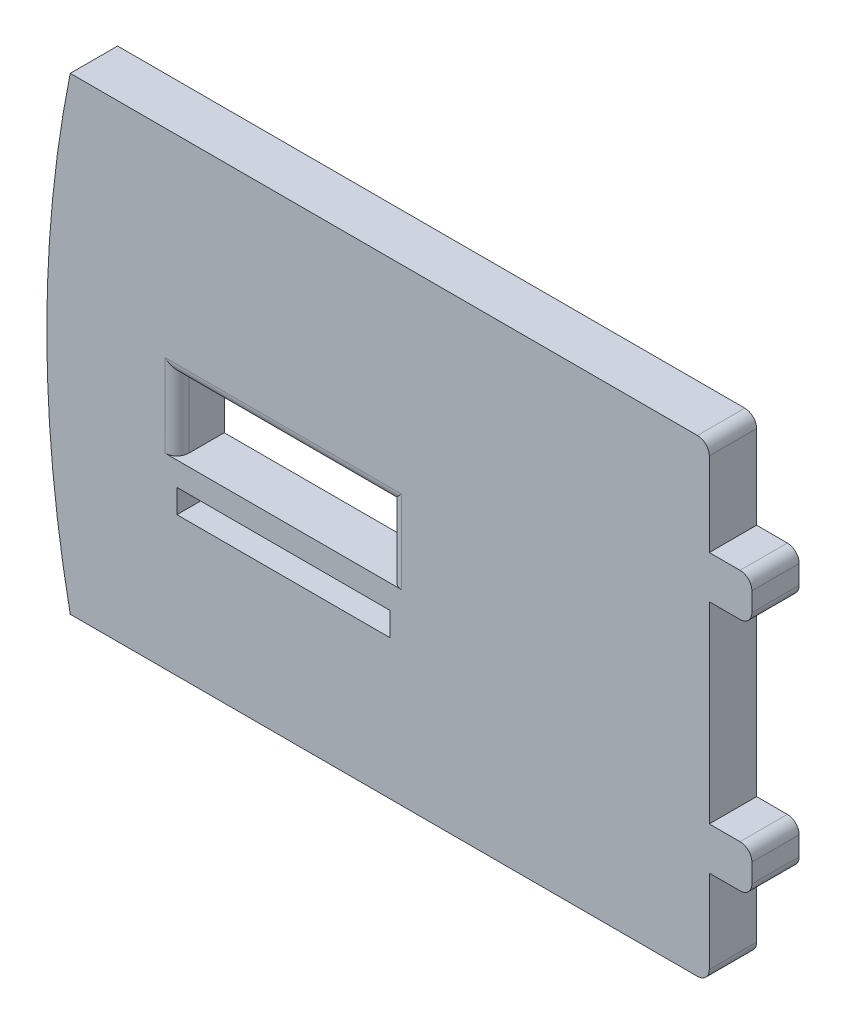
SolidWorks part; units mm, degrees
note: The reader was unsure of these and kept them because the rebuilt part matched: shared geometry of "Sketch1<3>", "Sketch1<4>", "Sketch1<9>".
ref_plane "Front Plane" through (0, 0, 0) normal (0, 0, 1) x (1, 0, 0)
ref_plane "Top Plane" through (0, 0, 0) normal (0, 1, 0) x (1, 0, 0)
ref_plane "Right Plane" through (0, 0, 0) normal (1, 0, 0) x (0, 0, -1)
sketch "Sketch1" plane through (0, 0, 0) normal (0, 0, 1) x (1, 0, 0)
  line L0 (0, 0) -> (-40, 0)
  line L1 (0, 0) -> (20, 0)
  line L2 (-10, 0) -> (-10, 9.9)
  line L3 (-44.5, 2) -> (-35.5, 2)
  line L4 (-44.5, 2) -> (-44.5, -2)
  line L5 (-44.5, -2) -> (-35.5, -2)
  line L6 (-35.5, 2) -> (-35.5, -2)
  line L7 (-44.5, 2) -> (-35.5, -2) construction
  line L8 (-44.5, -2) -> (-35.5, 2) construction
  line L10 (-10, 0) -> (-10, -9.9)
  line L13 (-22, 9.9) -> (-22, -9.9)
  line L14 (-10, 0) -> (-10, 9.9)
  line L15 (-10, 0) -> (-10, -9.9)
  line L16 (-10, -9.9) -> (-49.0101, -9.9)
  line L17 (-10, 9.9) -> (-49.0101, 9.9)
  circle A0 centre (0, 0) radius 50
  circle A1 centre (0, 0) radius 10
  dimension "D1" = 100
  dimension "D5" = 20
  dimension "D2" = 4
  dimension "D3" = 9
  dimension "D4" = 40
extrude "Boss-Extrude1" add sketch "Sketch1" against normal blind 2 contours A0
extrude "Boss-Extrude2" add sketch "Sketch1<3>" along normal blind 5
sketch "Sketch1<3>" plane through (0, 0, 0) normal (0, 0, 1) x (1, 0, 0) same geometry as "Sketch1"
ref_plane "Plane1" through (-35.5, 0, 0) normal (1, 0, 0) x (0, 0, -1)
sketch "Sketch2" plane through (-35.5, 0, 0) normal (1, 0, 0) x (0, 0, -1)
  line L0 (-5, 2) -> (0, -2)
  line L1 (0, 0) -> (-2.5, 0)
  line L2 (-2.5, 0) -> (-2.5, -2)
  line L3 (-5, -2) -> (0, -2) construction
ref_plane "Plane2" through (-44.5, 0, 0) normal (-1, 0, 0) x (0, 0, 1)
sketch "Sketch4" plane through (-44.5, 0, 0) normal (-1, 0, 0) x (0, 0, 1)
  line L0 (0, -2) -> (2.5, 0)
  line L1 (2.5, 0) -> (2.5, -2)
  line L2 (2.5, 0) -> (0, 0)
  line L3 (0, 2) -> (5, 2)
  line L4 (5, 2) -> (5, -2)
  line L5 (5, -2) -> (0, -2)
  line L6 (0, 2) -> (0, -2)
extrude "Cut-Extrude1" cut sketch "Sketch4" against normal blind 9 contours L3 L6 L2 L1 L5 L4 | L2 L6 L0
sketch "Sketch5" plane through (0, 0, 0) normal (0, 0, 1) x (1, 0, 0)
  line L0 (-35.5, -2) -> (-11.5, -2)
  line L1 (-35.5, 2) -> (-35.5, -2) construction
  line L2 (-35.5, -2) -> (-44.5, -2) construction
  line L3 (-11.5, -2) -> (-11.5, 0)
  line L4 (-11.5, 0) -> (-35.5, 0)
  line L5 (-35.5, -2) -> (-35.5, 0)
extrude "Boss-Extrude3" add sketch "Sketch5" along normal blind 2.5
extrude "Cut-Extrude7" cut sketch "Sketch1<4>" against normal blind 2 contours L1 A1 L0 | L0 A1 L1
sketch "Sketch1<4>" plane through (0, 0, 0) normal (0, 0, 1) x (1, 0, 0) same geometry as "Sketch1"
sketch "Sketch7" plane through (0, 0, 0) normal (0, 0, 1) x (1, 0, 0)
  line L0 (-10, 0) -> (-10, 4.9)
  line L1 (-10, 0) -> (-10, -4.9)
  line L2 (-10, 4.9) -> (-49.7593, 4.9)
  line L3 (-10, -4.9) -> (-49.7593, -4.9)
  line L4 (-10, 4.9) -> (-8, 4.9)
  line L5 (-8, 4.9) -> (-8, -4.9)
  circle A0 centre (0, 0) radius 10 construction
  circle A1 centre (0, 0) radius 50 construction
sketch "Sketch8" plane through (0, 0, 0) normal (0, 0, 1) x (1, 0, 0)
  line L0 (-11.5, -2) -> (-11.5, -4)
  line L1 (-11.5, -4) -> (-44.5, -4)
  line L2 (-44.5, 2.2) -> (-44.5, -2.2) construction
  line L3 (-44.5, -4) -> (-44.5, -2)
  line L4 (-44.5, -2) -> (-11.5, -2)
extrude "Boss-Extrude4" add sketch "Sketch8" along normal blind 2.5
sketch "Sketch13" plane through (0, 0, 0) normal (0, 1, 0) x (1, 0, 0)
  line L0 (-11.5, -2.5) -> (-11.5, 0)
  line L1 (-11.5, 0) -> (-35.5, 0)
  line L2 (-35.5, -5) -> (-35.5, 0) construction
  line L3 (-10, 0) -> (-49.7593, 0) construction
  line L4 (-35.5, 0) -> (-35.5, -2.5)
  line L5 (-35.5, -2.5) -> (-11.5, -2.5)
extrude "Cut-Extrude10" cut sketch "Sketch13" against normal blind 4
sketch "Sketch14" plane through (0, 0, 2.5) normal (0, 0, 1) x (1, 0, 0)
  line L0 (-44.5, -4) -> (-35.5, -4)
  line L1 (-44.5, 2.2) -> (-44.5, -2.2) construction
  line L2 (-44.5, -4) -> (-35.5, -4) construction
  line L3 (-35.5, -2.2) -> (-35.5, 2.2) construction
  line L4 (-35.5, -4) -> (-35.5, 0)
  line L5 (-35.5, 2) -> (-35.5, -2) construction
  line L6 (-35.5, 0) -> (-44.5, 0)
  line L7 (-35.5, 0) -> (-44.5, 0) construction
  line L8 (-44.5, 0) -> (-44.5, -4)
sketch "Sketch15" plane through (0, 0, -2) normal (0, 0, -1) x (-1, 0, 0)
  line L6 (44.5, -2) -> (35.5, -2)
  line L7 (44.5, 0) -> (44.5, -4) construction
  line L13 (35.5, -2) -> (35.5, 1)
  line L14 (35.5, 2) -> (35.5, -2) construction
  line L15 (35.5, 1) -> (44.5, 1)
  line L16 (44.5, 2) -> (44.5, -2) construction
  line L17 (44.5, 1) -> (44.5, -2)
  line L18 (44.5, -4) -> (44.5, -3)
  line L19 (44.5, -3) -> (35.5, -3)
  line L20 (35.5, -4) -> (35.5, 0) construction
  line L21 (35.5, -3) -> (35.5, -4)
  line L22 (35.5, -4) -> (44.5, -4)
  dimension "D1" = 3
extrude "Cut-Extrude17" cut sketch "Sketch1<9>" against normal blind 2
sketch "Sketch1<9>" plane through (0, 0, 0) normal (0, 0, 1) x (1, 0, 0) same geometry as "Sketch1"
chamfer "Chamfer2" distance 4.5 angle 35 1 edges at (-35.5, -1, 1.25) first distance on face at (-40, -1, 1.25)
sketch "Sketch17" plane through (-44.5, 0, 0) normal (-1, 0, 0) x (0, 0, 1)
  line L0 (-2, -3) -> (0, -3)
  line L1 (-2, -3) -> (-2, -4) construction
  line L2 (-2, -4) -> (-2, -3) construction
  line L3 (0, -10) -> (0, 10) construction
  line L4 (2.5, 0) -> (0, -2)
  line L5 (5, 2) -> (0, -2) construction
  line L6 (0, -2) -> (0, -4)
  line L7 (0, -4) -> (2.5, -4)
  line L8 (2.5, -4) -> (2.5, 0)
extrude "Cut-Extrude19" cut sketch "Sketch17" against normal blind 9 contours L7 L8 L4 L6
extrude "Cut-Extrude20" cut sketch "Sketch15" against normal blind 2
sketch "Sketch18" plane through (-22, 0, 0) normal (1, 0, 0) x (0, 0, -1)
  line L0 (2, 0) -> (2, 10)
  line L1 (2, 9.9) -> (2, -9.9) construction
  line L2 (2, 0) -> (2, -10)
  line L3 (2, -10) -> (0, -10)
  line L4 (0, 50) -> (0, -50) construction
  line L5 (0, -10) -> (0, 10)
  line L6 (0, 10) -> (2, 10)
  line L7 (1, 10) -> (1, 4.9642)
  line L8 (1, -10) -> (1, -4.9691)
  line L9 (0, 5.8642) -> (2, 5.8642)
  line L10 (0, 5.8642) -> (0, 4.0642)
  line L11 (0, 4.0642) -> (2, 4.0642)
  line L12 (2, 5.8642) -> (2, 4.0642)
  line L13 (0, 5.8642) -> (2, 4.0642) construction
  line L14 (0, 4.0642) -> (2, 5.8642) construction
  line L16 (0, -4.0691) -> (2, -4.0691)
  line L17 (0, -4.0691) -> (0, -5.8691)
  line L18 (0, -5.8691) -> (2, -5.8691)
  line L19 (2, -4.0691) -> (2, -5.8691)
  line L20 (0, -4.0691) -> (2, -5.8691) construction
  line L21 (0, -5.8691) -> (2, -4.0691) construction
  dimension "D1" = 1.8
  dimension "D2" = 1.8
extrude "Boss-Extrude6" add sketch "Sketch18" along normal blind 1.8
fillet "Fillet4" radius 0.5 9 edges at (-20.2, -4.0691, -1) (-20.2, -5.8691, -1) (-22, -9.9, -1) (-20.2, 4.0642, -1) (-20.2, 5.8642, -1) (-22, 9.9, -1) (-35.5, -0.5, 0) (-44.5, -0.5, 0) (-40, 1, 0)
